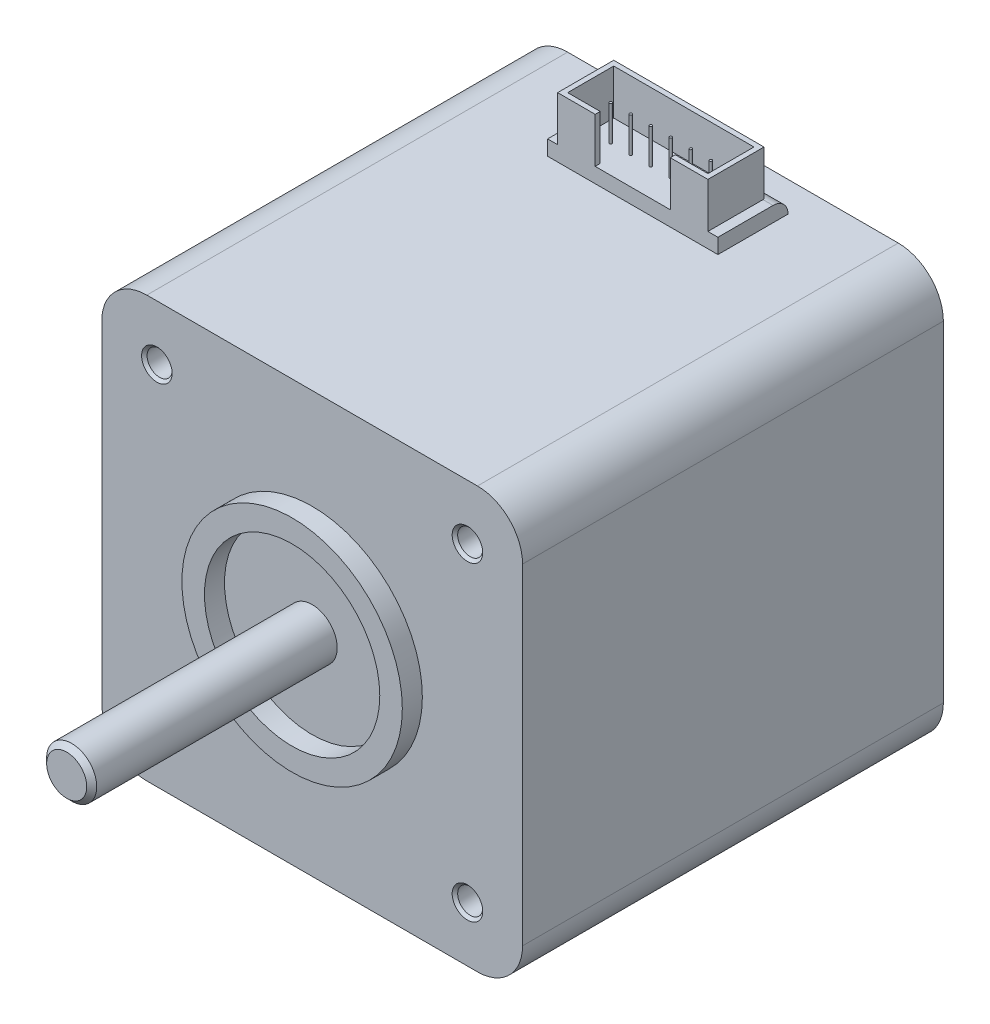
SolidWorks part; units mm, degrees
material "1060 Alloy"
ref_plane "Front Plane" through (0, 0, 0) normal (0, 0, 1) x (1, 0, 0)
ref_plane "Top Plane" through (0, 0, 0) normal (0, 1, 0) x (1, 0, 0)
ref_plane "Right Plane" through (0, 0, 0) normal (1, 0, 0) x (0, 0, -1)
sketch "Sketch1" plane through (0, 0, 0) normal (0, 0, 1) x (1, 0, 0)
  line L1 (-29.6154, 19.2115) -> (12.3846, 19.2115)
  line L2 (-29.6154, 19.2115) -> (-29.6154, -22.7885)
  line L3 (-29.6154, -22.7885) -> (12.3846, -22.7885)
  line L4 (12.3846, 19.2115) -> (12.3846, -22.7885)
  dimension "D1" = 42
  dimension "D2" = 42
extrude "Boss-Extrude2" add sketch "Sketch1" along normal blind 8
sketch "Sketch2" plane through (0, 0, 8) normal (0, 0, 1) x (1, 0, 0)
  line L0 (12.3846, -22.7885) -> (12.3846, 19.2115) construction
  line L1 (-29.6154, -1.7885) -> (12.3846, -1.7885) construction
  line L2 (-29.6154, 19.2115) -> (-29.6154, -22.7885) construction
  circle A0 centre (-8.6154, -1.7885) radius 11
  point P9 (-8.6154, -1.7885)
  dimension "D1" = 22
extrude "Boss-Extrude3" add sketch "Sketch2" along normal blind 2
sketch "Sketch4" plane through (0, 0, 0) normal (0, 0, -1) x (-1, 0, 0)
  line L1 (-12.3846, 19.2115) -> (29.6154, 19.2115)
  line L2 (-12.3846, 19.2115) -> (-12.3846, -22.7885)
  line L3 (-12.3846, -22.7885) -> (29.6154, -22.7885)
  line L4 (29.6154, 19.2115) -> (29.6154, -22.7885)
extrude "Boss-Extrude5" add sketch "Sketch4" along normal blind 24
sketch "Sketch5" plane through (0, 0, -24) normal (0, 0, -1) x (-1, 0, 0)
  line L1 (-12.3846, 19.2115) -> (29.6154, 19.2115)
  line L2 (-12.3846, 19.2115) -> (-12.3846, -22.7885)
  line L3 (-12.3846, -22.7885) -> (29.6154, -22.7885)
  line L4 (29.6154, 19.2115) -> (29.6154, -22.7885)
extrude "Boss-Extrude6" add sketch "Sketch5" along normal blind 10
fillet "Fillet1" radius 4.5 4 edges at (12.3846, 19.2115, -13) (-29.6154, -22.7885, -13) (12.3846, -22.7885, -13) (-29.6154, 19.2115, -13)
sketch "Sketch7" plane through (0, 0, -34) normal (0, 0, -1) x (-1, 0, 0)
  line L0 (-12.3846, -1.7885) -> (29.6154, -1.7885) construction
  line L1 (-12.3846, 14.7115) -> (-12.3846, -18.2885) construction
  line L2 (29.6154, -18.2885) -> (29.6154, 14.7115) construction
  circle A0 centre (8.6154, -1.7885) radius 8.75
  point P10 (8.6154, -1.7885)
  dimension "D1" = 17.5
extrude "Cut-Extrude1" cut sketch "Sketch7" against normal blind 2
sketch "Sketch8" plane through (0, 0, 10) normal (0, 0, 1) x (1, 0, 0)
  circle A0 centre (-8.6154, -1.7885) radius 8.75
  dimension "D1" = 17.5
extrude "Cut-Extrude2" cut sketch "Sketch8" against normal blind 2
sketch "Sketch9" plane through (0, 0, 8) normal (0, 0, 1) x (1, 0, 0)
  circle A0 centre (-8.6154, -1.7885) radius 2.5
  dimension "D1" = 5
extrude "Boss-Extrude9" add sketch "Sketch9" along normal blind 24.5
chamfer "Chamfer2" distance 0.5 angle 45 1 edges at (-6.1154, -1.7885, 32.5)
sketch "Sketch10" plane through (0, 0, 8) normal (0, 0, 1) x (1, 0, 0)
  line L0 (12.3846, -18.2885) -> (12.3846, 14.7115) construction
  line L1 (-24.1154, 13.7115) -> (6.8846, 13.7115) construction
  line L2 (-24.1154, 13.7115) -> (-24.1154, -17.2885) construction
  line L3 (-24.1154, -17.2885) -> (6.8846, -17.2885) construction
  line L4 (6.8846, 13.7115) -> (6.8846, -17.2885) construction
  line L5 (-25.1154, -22.7885) -> (7.8846, -22.7885) construction
  circle A0 centre (-24.1154, 13.7115) radius 1.6 construction
  circle A1 centre (-24.1154, -17.2885) radius 1.6 construction
  circle A2 centre (6.8846, -17.2885) radius 1.6 construction
  circle A3 centre (6.8846, 13.7115) radius 1.6 construction
  dimension "D1" = 3.2
  dimension "D2" = 31
  dimension "D3" = 31
  dimension "D4" = 5.5
  dimension "D5" = 5.5
hole_wizard "M3x0.5 Tapped Hole1" positions "3DSketch1" profile "Sketch11" tap size "M3x0.5" standard "ANSI Metric"
sketch3d "3DSketch1"
  point P0 (-24.1154, 13.7115, 8)
  point P3 (6.8846, 13.7115, 8)
  point P6 (6.8846, -17.2885, 8)
  point P9 (-24.1154, -17.2885, 8)
sketch "Sketch11" plane through (-24.1154, 13.7115, 8) normal (1, 0, 0) x (0, -1, 0)
  line L0 (0, 0) -> (0, 6.5011)
  line L1 (0, 6.5011) -> (1.25, 5.75)
  line L2 (1.25, 5.75) -> (1.25, 0.275)
  line L3 (1.25, 0.275) -> (1.525, 0)
  line L5 (1.525, 0) -> (0, 0)
  line L6 (-1.25, 0.275) -> (-1.525, 0) construction
  line L10 (0, 6.5011) -> (-1.25, 5.75) construction
  line L11 (0, -6.35) -> (0, 107.95) construction
  dimension "Tap Drill Dia." = 2.5
  dimension "Tap Drill Depth" = 5.75
  dimension "Near C'Sink Dia." = 3.05
  dimension "Near C'Sink Angle" = 90
  dimension "Drill Angle" = 118
cosmetic thread "Hole Thread1" parameters "D1"=4, "D2"=3
cosmetic thread "Hole Thread2" parameters "D1"=4, "D2"=3
cosmetic thread "Hole Thread3" parameters "D1"=4, "D2"=3
cosmetic thread "Hole Thread4" parameters "D1"=4, "D2"=3
sketch "Sketch12" plane through (0, 19.2115, 0) normal (0, 1, 0) x (1, 0, 0)
  line L0 (12.3846, 34) -> (-29.6154, 34) construction
  line L1 (-17.1154, 31) -> (-0.1154, 31)
  line L2 (-17.1154, 31) -> (-17.1154, 24)
  line L3 (-17.1154, 24) -> (-0.1154, 24)
  line L4 (-0.1154, 31) -> (-0.1154, 24)
  line L5 (12.3846, -8) -> (12.3846, 34) construction
  point P6 (-8.6154, 31)
  dimension "D1" = 17
  dimension "D2" = 7
  dimension "D3" = 10
  dimension "D4" = 21
extrude "Boss-Extrude10" add sketch "Sketch12" along normal blind 1.5
fillet "Fillet2" radius 1.5 1 edges at (-8.6154, 20.7115, -31)
sketch "Sketch13" plane through (0, 20.7115, 0) normal (0, 1, 0) x (1, 0, 0)
  line L0 (-17.1154, 24) -> (-0.1154, 24) construction
  line L1 (-16.1154, 29.6) -> (-1.1154, 29.6)
  line L2 (-16.1154, 29.6) -> (-16.1154, 24)
  line L3 (-16.1154, 24) -> (-1.1154, 24)
  line L4 (-1.1154, 29.6) -> (-1.1154, 24)
  line L7 (-17.1154, 31) -> (-17.1154, 24) construction
  point P12 (-8.6154, 24)
  dimension "D1" = 15
  dimension "D2" = 5.6
  dimension "D3" = 8.5
extrude "Boss-Extrude11" add sketch "Sketch13" along normal blind 4.5
sketch "Sketch15" plane through (0, 25.2115, 0) normal (0, 1, 0) x (1, 0, 0)
  line L0 (-12.3654, 24) -> (-12.3654, 24.5)
  line L1 (-16.1154, 24) -> (-1.1154, 24) construction
  line L2 (-12.3654, 24.5) -> (-15.6154, 24.5)
  line L3 (-15.6154, 24.5) -> (-15.6154, 29.1)
  line L4 (-15.6154, 29.1) -> (-1.6154, 29.1)
  line L5 (-1.6154, 29.1) -> (-1.6154, 24.5)
  line L6 (-1.6154, 24.5) -> (-4.8654, 24.5)
  line L7 (-4.8654, 24.5) -> (-4.8654, 24)
  line L8 (-17.1154, 24) -> (-0.1154, 24) construction
  line L9 (-12.3654, 24) -> (-4.8654, 24)
  line L10 (-1.1154, 24) -> (-1.1154, 29.5) construction
  line L11 (-1.1154, 29.6) -> (-16.1154, 29.6) construction
  dimension "D1" = 7.5
  dimension "D2" = 14
  dimension "D3" = 0.5
  dimension "D4" = 0.5
  dimension "D5" = 3.25
  dimension "D6" = 0.5
extrude "Cut-Extrude3" cut sketch "Sketch15" against normal blind 4.5
sketch "Sketch16" plane through (0, 20.7115, 0) normal (0, 1, 0) x (1, 0, 0)
  line L0 (-1.6154, 29.1) -> (-15.6154, 29.1) construction
  line L1 (-15.6154, 29.1) -> (-15.6154, 24.5) construction
  circle A0 centre (-13.6154, 26.8) radius 0.125
  dimension "D1" = 0.25
  dimension "D2" = 2.3
  dimension "D3" = 2
extrude "Boss-Extrude12" add sketch "Sketch16" along normal blind 3.5 contours A0
pattern_linear "LPattern1" count 6 spacing 2 along (1, 0, 0) of "Boss-Extrude12"
